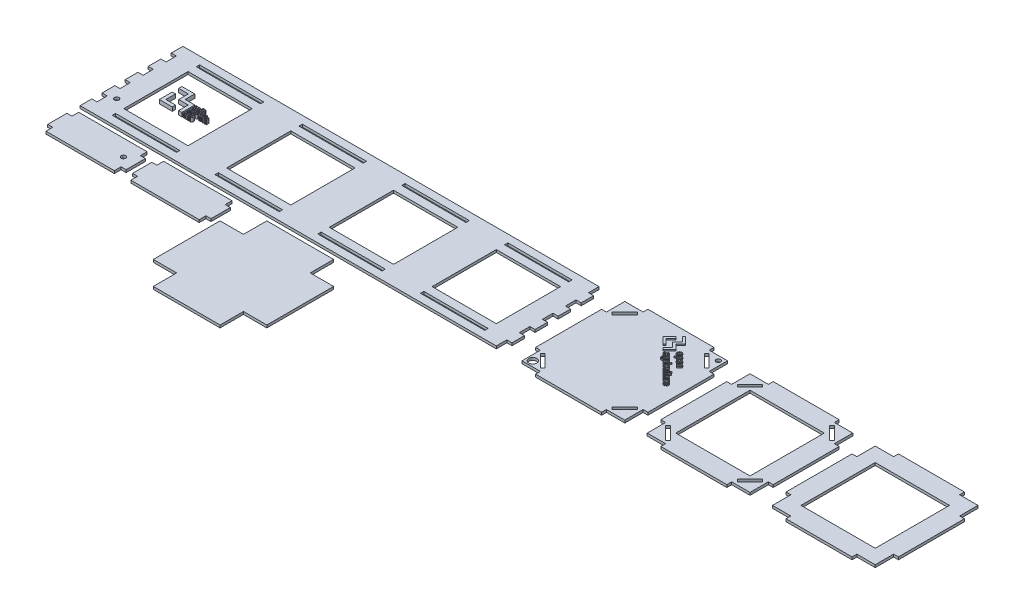
SolidWorks part; units mm, degrees
ref_plane "Front" through (0, 0, 0) normal (0, 0, 1) x (1, 0, 0)
ref_plane "Top" through (0, 0, 0) normal (0, 1, 0) x (1, 0, 0)
ref_plane "Right" through (0, 0, 0) normal (1, 0, 0) x (0, 0, -1)
sketch "Sketch1" plane through (0, 0, 0) normal (0, 1, 0) x (1, 0, 0)
  line L0 (0, 0) -> (152.4, 0) construction
  line L2 (-50.8, 50.8) -> (-50.8, -50.8) construction
  line L4 (50.8, 50.8) -> (50.8, -50.8) construction
  line L5 (-50.8, 50.8) -> (50.8, -50.8) construction
  line L6 (-50.8, -50.8) -> (50.8, 50.8) construction
  line L11 (50.8, 50.8) -> (152.4, 50.8)
  line L12 (50.8, 50.8) -> (50.8, -50.8) construction
  line L13 (50.8, -50.8) -> (152.4, -50.8)
  line L14 (152.4, 50.8) -> (152.4, -50.8) construction
  line L19 (-50.8, -50.8) -> (-152.4, -50.8)
  line L20 (-50.8, -50.8) -> (-50.8, 50.8) construction
  line L21 (-50.8, 50.8) -> (-152.4, 50.8)
  line L28 (50.8, -50.8) -> (-50.8, -50.8)
  line L34 (50.8, 50.8) -> (-50.8, 50.8)
  line L35 (-152.4, 50.8) -> (-152.4, -50.8) construction
  line L43 (-152.4, 50.8) -> (-254, 50.8)
  line L44 (-254, 50.8) -> (-254, -50.8) construction
  line L45 (-254, -50.8) -> (-152.4, -50.8)
  line L46 (152.4, 50.8) -> (152.4, 40.3352)
  line L47 (152.4, 40.3352) -> (157.48, 40.3352)
  line L48 (157.48, 40.3352) -> (157.48, 28.0162)
  line L49 (157.48, 28.0162) -> (152.4, 28.0162)
  line L50 (152.4, 28.0162) -> (152.4, 17.5514)
  line L51 (152.4, 17.5514) -> (157.48, 17.5514)
  line L63 (157.48, 17.5514) -> (157.48, 5.2324)
  line L64 (157.48, 5.2324) -> (152.4, 5.2324)
  line L65 (152.4, 5.2324) -> (152.4, -5.2324)
  line L66 (152.4, -5.2324) -> (157.48, -5.2324)
  line L67 (157.48, -5.2324) -> (157.48, -17.5514)
  line L68 (157.48, -17.5514) -> (152.4, -17.5514)
  line L69 (152.4, -17.5514) -> (152.4, -28.0162)
  line L70 (152.4, -28.0162) -> (157.48, -28.0162)
  line L71 (157.48, -28.0162) -> (157.48, -40.3352)
  line L72 (157.48, -40.3352) -> (152.4, -40.3352)
  line L73 (152.4, -40.3352) -> (152.4, -50.8)
  line L74 (-254, 50.8) -> (-259.08, 50.8)
  line L76 (-259.08, 39.2557) -> (-254, 39.2557)
  line L78 (-254, 29.0957) -> (-259.08, 29.0957)
  line L80 (-259.08, 16.4719) -> (-254, 16.4719)
  line L82 (-254, 6.3119) -> (-259.08, 6.3119)
  line L84 (-259.08, -6.3119) -> (-254, -6.3119)
  line L86 (-254, -16.4719) -> (-259.08, -16.4719)
  line L88 (-259.08, -29.0957) -> (-254, -29.0957)
  line L90 (-254, -39.2557) -> (-259.08, -39.2557)
  line L92 (-259.08, -50.8) -> (-254, -50.8)
  line L93 (157.48, 11.3919) -> (-254, 11.3919) construction
  line L94 (-254, 34.1757) -> (157.48, 34.1757) construction
  line L95 (-259.08, 50.8) -> (-259.08, 39.2557)
  line L96 (-259.08, 29.0957) -> (-259.08, 16.4719)
  line L97 (-254, 39.2557) -> (-254, 29.0957)
  line L98 (-254, 16.4719) -> (-254, 6.3119)
  line L99 (-254, -6.3119) -> (-254, -16.4719)
  line L100 (-254, -29.0957) -> (-254, -39.2557)
  line L101 (-254, -34.1757) -> (157.48, -34.1757) construction
  line L102 (-254, -11.3919) -> (157.48, -11.3919) construction
  line L103 (-259.08, 6.3119) -> (-259.08, -6.3119)
  line L104 (-259.08, -16.4719) -> (-259.08, -29.0957)
  line L105 (-259.08, -39.2557) -> (-259.08, -50.8)
  point P0 (0, 0)
  dimension "D1" = 101.6
  dimension "D2" = 101.6
  dimension "D3" = 5.08
  dimension "D4" = 12.319
  dimension "D5" = 10.16
extrude "Boss-Extrude1" add sketch "Sketch1" along normal blind 2.54
sketch "Sketch4" plane through (0, 2.54, 0) normal (0, 1, 0) x (1, 0, 0)
  line L0 (-152.4, 50.8) -> (-152.4, -50.8) construction
  line L1 (-152.4, 50.8) -> (-152.4, -50.8)
  line L2 (-50.8, 50.8) -> (-50.8, -50.8) construction
  line L3 (-50.8, 50.8) -> (-50.8, -50.8)
  line L4 (50.8, 50.8) -> (50.8, -50.8) construction
  line L5 (50.8, 50.8) -> (50.8, -50.8)
sketch "Sketch5" plane through (0, 2.54, 0) normal (0, 1, 0) x (1, 0, 0)
  line L0 (-254, -6.3119) -> (-254, 6.3119) construction
  line L1 (-152.4, 0) -> (-254, 0) construction
  line L2 (-152.4, 50.8) -> (-152.4, -50.8) construction
  line L3 (-152.4, 0) -> (-50.8, 0) construction
  line L4 (-50.8, 50.8) -> (-50.8, -50.8) construction
  line L5 (-50.8, 0) -> (50.8, 0) construction
  line L6 (50.8, 50.8) -> (50.8, -50.8) construction
  line L7 (50.8, 0) -> (152.4, 0) construction
  line L8 (152.4, -5.2324) -> (152.4, 5.2324) construction
  line L9 (-203.2, 0) -> (-203.2, -50.8) construction
  line L10 (-259.08, -50.8) -> (152.4, -50.8) construction
  line L11 (-101.6, 0) -> (-101.6, -50.8) construction
  line L12 (0, 0) -> (0, -50.8) construction
  line L13 (101.6, 0) -> (101.6, -50.8) construction
  line L14 (-171.45, -43.18) -> (-171.45, -50.8) construction
  line L15 (-234.95, -39.878) -> (-171.45, -39.878)
  line L16 (-234.95, -39.878) -> (-234.95, -43.18)
  line L17 (-234.95, -43.18) -> (-171.45, -43.18)
  line L18 (-171.45, -39.878) -> (-171.45, -43.18)
  line L19 (-234.95, -39.878) -> (-171.45, -43.18) construction
  line L20 (-234.95, -43.18) -> (-171.45, -39.878) construction
  line L21 (-133.35, -39.878) -> (-69.85, -39.878)
  line L22 (-133.35, -39.878) -> (-133.35, -43.18)
  line L23 (-133.35, -43.18) -> (-69.85, -43.18)
  line L24 (-69.85, -39.878) -> (-69.85, -43.18)
  line L25 (-133.35, -39.878) -> (-69.85, -43.18) construction
  line L26 (-133.35, -43.18) -> (-69.85, -39.878) construction
  line L27 (-31.75, -43.18) -> (31.75, -43.18)
  line L28 (-31.75, -43.18) -> (-31.75, -39.878)
  line L29 (-31.75, -39.878) -> (31.75, -39.878)
  line L30 (31.75, -43.18) -> (31.75, -39.878)
  line L31 (-31.75, -43.18) -> (31.75, -39.878) construction
  line L32 (-31.75, -39.878) -> (31.75, -43.18) construction
  line L33 (69.85, -43.18) -> (133.35, -43.18)
  line L34 (69.85, -43.18) -> (69.85, -39.878)
  line L35 (69.85, -39.878) -> (133.35, -39.878)
  line L36 (133.35, -43.18) -> (133.35, -39.878)
  line L37 (69.85, -43.18) -> (133.35, -39.878) construction
  line L38 (69.85, -39.878) -> (133.35, -43.18) construction
  line L39 (69.85, 39.878) -> (133.35, 43.18) construction
  line L40 (69.85, 43.18) -> (133.35, 39.878) construction
  line L41 (-31.75, 39.878) -> (31.75, 43.18) construction
  line L42 (-31.75, 43.18) -> (31.75, 39.878) construction
  line L43 (-133.35, 43.18) -> (-69.85, 39.878) construction
  line L44 (-133.35, 39.878) -> (-69.85, 43.18) construction
  line L45 (-234.95, 43.18) -> (-171.45, 39.878) construction
  line L46 (-234.95, 39.878) -> (-171.45, 43.18) construction
  line L47 (-171.45, 43.18) -> (-171.45, 50.8) construction
  line L48 (133.35, 43.18) -> (133.35, 39.878)
  line L49 (69.85, 39.878) -> (133.35, 39.878)
  line L50 (69.85, 43.18) -> (69.85, 39.878)
  line L51 (69.85, 43.18) -> (133.35, 43.18)
  line L52 (31.75, 43.18) -> (31.75, 39.878)
  line L53 (-31.75, 39.878) -> (31.75, 39.878)
  line L54 (-31.75, 43.18) -> (-31.75, 39.878)
  line L55 (-31.75, 43.18) -> (31.75, 43.18)
  line L56 (-69.85, 39.878) -> (-69.85, 43.18)
  line L57 (-133.35, 43.18) -> (-69.85, 43.18)
  line L58 (-133.35, 39.878) -> (-133.35, 43.18)
  line L59 (-133.35, 39.878) -> (-69.85, 39.878)
  line L60 (-171.45, 39.878) -> (-171.45, 43.18)
  line L61 (-234.95, 43.18) -> (-171.45, 43.18)
  line L62 (-234.95, 39.878) -> (-234.95, 43.18)
  line L63 (-234.95, 39.878) -> (-171.45, 39.878)
  line L65 (-234.95, 31.75) -> (-171.45, 31.75)
  line L66 (-234.95, 31.75) -> (-234.95, -31.75)
  line L67 (-234.95, -31.75) -> (-171.45, -31.75)
  line L68 (-171.45, 31.75) -> (-171.45, -31.75)
  line L69 (-234.95, 31.75) -> (-171.45, -31.75) construction
  line L70 (-234.95, -31.75) -> (-171.45, 31.75) construction
  line L71 (-133.35, 31.75) -> (-69.85, 31.75)
  line L72 (-133.35, 31.75) -> (-133.35, -31.75)
  line L73 (-133.35, -31.75) -> (-69.85, -31.75)
  line L74 (-69.85, 31.75) -> (-69.85, -31.75)
  line L75 (-133.35, 31.75) -> (-69.85, -31.75) construction
  line L76 (-133.35, -31.75) -> (-69.85, 31.75) construction
  line L77 (-31.75, 31.75) -> (31.75, 31.75)
  line L78 (-31.75, 31.75) -> (-31.75, -31.75)
  line L79 (-31.75, -31.75) -> (31.75, -31.75)
  line L80 (31.75, 31.75) -> (31.75, -31.75)
  line L81 (-31.75, 31.75) -> (31.75, -31.75) construction
  line L82 (-31.75, -31.75) -> (31.75, 31.75) construction
  line L83 (69.85, 31.75) -> (133.35, 31.75)
  line L84 (69.85, 31.75) -> (69.85, -31.75)
  line L85 (69.85, -31.75) -> (133.35, -31.75)
  line L86 (133.35, 31.75) -> (133.35, -31.75)
  line L87 (69.85, 31.75) -> (133.35, -31.75) construction
  line L88 (69.85, -31.75) -> (133.35, 31.75) construction
  circle A0 centre (-246.95, -26.75) radius 2.2225
  point P27 (-203.2, -41.529)
  point P32 (-101.6, -41.529)
  point P37 (0, -41.529)
  point P42 (101.6, -41.529)
  point P66 (101.6, 41.529)
  point P67 (0, 41.529)
  point P68 (-101.6, 41.529)
  point P69 (-203.2, 41.529)
  dimension "D5" = 4.445
  dimension "D7" = 5
  dimension "D1" = 7.62
  dimension "D2" = 3.302
  dimension "D3" = 63.5
  dimension "D4" = 63.5
  dimension "D6" = 12
extrude "Cut-Extrude2" cut sketch "Sketch5" against normal through all
sketch "Sketch6" plane through (0, 0, 0) normal (0, 1, 0) x (1, 0, 0)
  line L0 (0, 0) -> (228.6, 0) construction
  line L1 (228.6, 0) -> (228.6, 53.1812) construction
  line L2 (177.8, 50.8) -> (279.4, 50.8) construction
  line L3 (177.8, 50.8) -> (177.8, -50.8) construction
  line L4 (177.8, -50.8) -> (279.4, -50.8) construction
  line L5 (279.4, 50.8) -> (279.4, -50.8) construction
  line L6 (177.8, 50.8) -> (279.4, -50.8) construction
  line L7 (177.8, -50.8) -> (279.4, 50.8) construction
  line L8 (228.6, 0) -> (281.7812, 0) construction
  line L9 (228.6, 0) -> (228.6, -53.1812) construction
  line L10 (177.8, 32.639) -> (177.8, 50.8)
  line L11 (195.961, 55.5625) -> (261.239, 55.5625)
  line L12 (195.961, 55.5625) -> (195.961, 50.8)
  line L13 (195.961, 50.8) -> (261.239, 50.8) construction
  line L14 (261.239, 55.5625) -> (261.239, 50.8)
  line L15 (195.961, 55.5625) -> (261.239, 50.8) construction
  line L16 (195.961, 50.8) -> (261.239, 55.5625) construction
  line L17 (284.1625, -32.639) -> (279.4, -32.639)
  line L18 (284.1625, -32.639) -> (284.1625, 32.639)
  line L19 (284.1625, 32.639) -> (279.4, 32.639)
  line L20 (279.4, -32.639) -> (279.4, 32.639) construction
  line L21 (284.1625, -32.639) -> (279.4, 32.639) construction
  line L22 (284.1625, 32.639) -> (279.4, -32.639) construction
  line L23 (195.961, -55.5625) -> (261.239, -55.5625)
  line L24 (195.961, -55.5625) -> (195.961, -50.8)
  line L25 (195.961, -50.8) -> (261.239, -50.8) construction
  line L26 (261.239, -55.5625) -> (261.239, -50.8)
  line L27 (195.961, -55.5625) -> (261.239, -50.8) construction
  line L28 (195.961, -50.8) -> (261.239, -55.5625) construction
  line L29 (173.0375, 32.639) -> (177.8, 32.639)
  line L30 (173.0375, 32.639) -> (173.0375, -32.639)
  line L31 (173.0375, -32.639) -> (177.8, -32.639)
  line L32 (177.8, 32.639) -> (177.8, -32.639) construction
  line L33 (173.0375, 32.639) -> (177.8, -32.639) construction
  line L34 (173.0375, -32.639) -> (177.8, 32.639) construction
  line L35 (177.8, 50.8) -> (195.961, 50.8)
  line L36 (261.239, 50.8) -> (279.4, 50.8)
  line L37 (279.4, 50.8) -> (279.4, 32.639)
  line L38 (279.4, -32.639) -> (279.4, -50.8)
  line L39 (279.4, -50.8) -> (261.239, -50.8)
  line L40 (195.961, -50.8) -> (177.8, -50.8)
  line L41 (177.8, -50.8) -> (177.8, -32.639)
  line L42 (296.8625, 32.639) -> (296.8625, -32.639)
  line L43 (296.8625, 32.639) -> (301.625, 32.639)
  line L44 (301.625, 32.639) -> (301.625, 50.8)
  line L45 (301.625, 50.8) -> (319.786, 50.8)
  line L46 (319.786, 55.5625) -> (319.786, 50.8)
  line L47 (319.786, 55.5625) -> (385.064, 55.5625)
  line L48 (385.064, 55.5625) -> (385.064, 50.8)
  line L49 (385.064, 50.8) -> (403.225, 50.8)
  line L50 (403.225, 50.8) -> (403.225, 32.639)
  line L51 (407.9875, 32.639) -> (403.225, 32.639)
  line L52 (407.9875, -32.639) -> (407.9875, 32.639)
  line L53 (407.9875, -32.639) -> (403.225, -32.639)
  line L54 (403.225, -32.639) -> (403.225, -50.8)
  line L55 (403.225, -50.8) -> (385.064, -50.8)
  line L56 (385.064, -55.5625) -> (385.064, -50.8)
  line L57 (319.786, -55.5625) -> (385.064, -55.5625)
  line L58 (319.786, -55.5625) -> (319.786, -50.8)
  line L59 (319.786, -50.8) -> (301.625, -50.8)
  line L60 (301.625, -50.8) -> (301.625, -32.639)
  line L61 (296.8625, -32.639) -> (301.625, -32.639)
  line L62 (301.625, 50.8) -> (403.225, -50.8) construction
  line L63 (420.6875, 32.639) -> (420.6875, -32.639)
  line L64 (420.6875, 32.639) -> (425.45, 32.639)
  line L65 (425.45, 32.639) -> (425.45, 50.8)
  line L66 (425.45, 50.8) -> (443.611, 50.8)
  line L67 (443.611, 55.5625) -> (443.611, 50.8)
  line L68 (443.611, 55.5625) -> (508.889, 55.5625)
  line L69 (508.889, 55.5625) -> (508.889, 50.8)
  line L70 (508.889, 50.8) -> (527.05, 50.8)
  line L71 (527.05, 50.8) -> (527.05, 32.639)
  line L72 (531.8125, 32.639) -> (527.05, 32.639)
  line L73 (531.8125, -32.639) -> (531.8125, 32.639)
  line L74 (531.8125, -32.639) -> (527.05, -32.639)
  line L75 (527.05, -32.639) -> (527.05, -50.8)
  line L76 (527.05, -50.8) -> (508.889, -50.8)
  line L77 (508.889, -55.5625) -> (508.889, -50.8)
  line L78 (443.611, -55.5625) -> (508.889, -55.5625)
  line L79 (443.611, -55.5625) -> (443.611, -50.8)
  line L80 (443.611, -50.8) -> (425.45, -50.8)
  line L81 (425.45, -50.8) -> (425.45, -32.639)
  line L82 (420.6875, -32.639) -> (425.45, -32.639)
  line L83 (425.45, 50.8) -> (527.05, -50.8) construction
  line L84 (315.722, 36.703) -> (389.128, 36.703)
  line L85 (315.722, 36.703) -> (315.722, -36.703)
  line L86 (315.722, -36.703) -> (389.128, -36.703)
  line L87 (389.128, 36.703) -> (389.128, -36.703)
  line L88 (315.722, 36.703) -> (389.128, -36.703) construction
  line L89 (315.722, -36.703) -> (389.128, 36.703) construction
  line L91 (512.953, 36.703) -> (439.547, 36.703)
  line L92 (512.953, 36.703) -> (512.953, -36.703)
  line L93 (512.953, -36.703) -> (439.547, -36.703)
  line L94 (439.547, 36.703) -> (439.547, -36.703)
  line L95 (512.953, 36.703) -> (439.547, -36.703) construction
  line L96 (512.953, -36.703) -> (439.547, 36.703) construction
  point P22 (175.4187, 0)
  point P67 (352.425, 0)
  point P72 (476.25, 0)
  dimension "D1" = 101.6
  dimension "D2" = 101.6
  dimension "D3" = 4.7625
  dimension "D4" = 65.278
  dimension "D5" = 228.6
  dimension "D7" = 12.7
  dimension "D8" = 73.406
  dimension "D6" = 3
extrude "Boss-Extrude2" add sketch "Sketch6" along normal blind 2.54 separate body
sketch "Sketch7" plane through (0, 0, 0) normal (0, 1, 0) x (1, 0, 0)
  line L0 (-234.95, 39.878) -> (-234.95, -27.686) construction
  line L1 (-254.08, -57.15) -> (-186.516, -57.15)
  line L2 (-254.08, -57.15) -> (-254.08, -63.8175)
  line L3 (-254.08, -89.535) -> (-186.516, -89.535)
  line L4 (-186.516, -57.15) -> (-186.516, -63.8175)
  line L5 (-254.08, -57.15) -> (-186.516, -89.535) construction
  line L6 (-254.08, -89.535) -> (-186.516, -57.15) construction
  line L7 (-234.95, 31.75) -> (-234.95, -31.75) construction
  line L8 (-234.95, -27.686) -> (-234.95, -31.75) construction
  line L9 (177.8, -32.639) -> (177.8, -50.8) construction
  line L10 (177.8, -50.8) -> (195.961, -50.8) construction
  line L12 (-254.08, -63.8175) -> (-259.08, -63.8175)
  line L13 (182.9292, -33.0985) -> (195.5015, -45.6708) construction
  line L14 (182.9292, -33.0985) -> (180.5943, -35.4333) construction
  line L15 (180.5943, -35.4333) -> (193.1667, -48.0057) construction
  line L16 (195.5015, -45.6708) -> (193.1667, -48.0057) construction
  line L17 (182.9292, -33.0985) -> (193.1667, -48.0057) construction
  line L18 (180.5943, -35.4333) -> (195.5015, -45.6708) construction
  line L19 (-259.08, -63.8175) -> (-259.08, -82.8675)
  line L20 (-259.08, -82.8675) -> (-254.08, -82.8675)
  line L21 (177.8, -32.639) -> (195.961, -50.8) construction
  line L22 (188.0479, -40.5521) -> (186.8805, -41.7195) construction
  line L23 (-254.08, -82.8675) -> (-254.08, -89.535)
  line L24 (-186.516, -63.8175) -> (-181.516, -63.8175)
  line L25 (-181.516, -63.8175) -> (-181.516, -82.8675)
  line L26 (-181.516, -82.8675) -> (-186.516, -82.8675)
  line L27 (-186.516, -82.8675) -> (-186.516, -89.535)
  line L28 (-259.08, -50.8) -> (152.4, -50.8) construction
  line L29 (-259.08, -39.2557) -> (-259.08, -50.8) construction
  line L30 (-170.166, -57.15) -> (-102.602, -57.15)
  line L31 (-170.166, -57.15) -> (-170.166, -63.8175)
  line L32 (-170.166, -89.535) -> (-102.602, -89.535)
  line L33 (-102.602, -57.15) -> (-102.602, -63.8175)
  line L34 (-170.166, -63.8175) -> (-175.166, -63.8175)
  line L35 (-175.166, -63.8175) -> (-175.166, -82.8675)
  line L36 (-175.166, -82.8675) -> (-170.166, -82.8675)
  line L37 (-170.166, -82.8675) -> (-170.166, -89.535)
  line L38 (-102.602, -63.8175) -> (-97.602, -63.8175)
  line L39 (-97.602, -63.8175) -> (-97.602, -82.8675)
  line L40 (-97.602, -82.8675) -> (-102.602, -82.8675)
  line L41 (-102.602, -82.8675) -> (-102.602, -89.535)
  line L42 (-170.166, -57.15) -> (-102.602, -89.535) construction
  line L43 (-170.166, -89.535) -> (-102.602, -57.15) construction
  point P0 (-220.298, -73.3425)
  point P14 (188.0479, -40.5521)
  point P38 (-136.384, -73.3425)
  dimension "D1" = 32.385
  dimension "D2" = 4.064
  dimension "D3" = 3.302
  dimension "D4" = 19.05
  dimension "D5" = 17.78
  dimension "D6" = 5
  dimension "D7" = 6.35
  dimension "D9" = 6.35
  dimension "D8" = 2
extrude "Boss-Extrude3" add sketch "Sketch7" along normal blind 2.54 separate body
sketch "Sketch8" plane through (0, 2.54, 0) normal (0, 1, 0) x (1, 0, 0)
  line L0 (180.5943, -35.4333) -> (193.1667, -48.0057) construction
  line L1 (195.5015, -45.6708) -> (193.1667, -48.0057) construction
  line L2 (182.9292, -33.0985) -> (195.5015, -45.6708) construction
  line L3 (182.9292, -33.0985) -> (180.5943, -35.4333) construction
  line L4 (180.5943, -35.4333) -> (193.1667, -48.0057)
  line L5 (195.5015, -45.6708) -> (193.1667, -48.0057)
  line L6 (182.9292, -33.0985) -> (195.5015, -45.6708)
  line L7 (182.9292, -33.0985) -> (180.5943, -35.4333)
  line L8 (177.8, 50.8) -> (279.4, -50.8) construction
  line L9 (195.5015, 45.6708) -> (182.9292, 33.0985)
  line L10 (195.5015, 45.6708) -> (193.1667, 48.0057)
  line L11 (193.1667, 48.0057) -> (180.5943, 35.4333)
  line L12 (182.9292, 33.0985) -> (180.5943, 35.4333)
  line L13 (274.2708, 33.0985) -> (261.6985, 45.6708)
  line L14 (274.2708, 33.0985) -> (276.6057, 35.4333)
  line L15 (276.6057, 35.4333) -> (264.0333, 48.0057)
  line L16 (261.6985, 45.6708) -> (264.0333, 48.0057)
  line L17 (261.6985, -45.6708) -> (274.2708, -33.0985)
  line L18 (261.6985, -45.6708) -> (264.0333, -48.0057)
  line L19 (264.0333, -48.0057) -> (276.6057, -35.4333)
  line L20 (274.2708, -33.0985) -> (276.6057, -35.4333)
  line L21 (301.625, -32.639) -> (319.786, -50.8) construction
  line L22 (304.4193, -35.4333) -> (306.7542, -33.0985)
  line L23 (306.7542, -33.0985) -> (319.3265, -45.6708)
  line L24 (319.3265, -45.6708) -> (316.9917, -48.0057)
  line L25 (310.7055, -41.7195) -> (313.0404, -39.3846) construction
  line L26 (304.4193, -35.4333) -> (316.9917, -48.0057)
  line L27 (301.625, 50.8) -> (403.225, -50.8) construction
  line L28 (306.7542, 33.0985) -> (304.4193, 35.4333)
  line L29 (316.9917, 48.0057) -> (304.4193, 35.4333)
  line L30 (316.9917, 48.0057) -> (319.3265, 45.6708)
  line L31 (319.3265, 45.6708) -> (306.7542, 33.0985)
  line L32 (385.5235, 45.6708) -> (387.8583, 48.0057)
  line L33 (400.4307, 35.4333) -> (387.8583, 48.0057)
  line L34 (400.4307, 35.4333) -> (398.0958, 33.0985)
  line L35 (398.0958, 33.0985) -> (385.5235, 45.6708)
  line L36 (398.0958, -33.0985) -> (400.4307, -35.4333)
  line L37 (387.8583, -48.0057) -> (400.4307, -35.4333)
  line L38 (387.8583, -48.0057) -> (385.5235, -45.6708)
  line L39 (385.5235, -45.6708) -> (398.0958, -33.0985)
  circle A0 centre (228.6, 0) radius 20.7898 construction
  circle A1 centre (228.6, 0) radius 20.7898 construction
  circle A2 centre (228.6, 0) radius 20.7898 construction
  circle A3 centre (228.6, 0) radius 20.7898 construction
  circle A4 centre (352.425, 0) radius 51.9059 construction
  point P28 (228.6, 0)
  point P58 (352.425, 0)
  dimension "D1" = 4
  dimension "D2" = 4
extrude "Cut-Extrude3" cut sketch "Sketch8" against normal through all
sketch "Sketch10" plane through (0, 2.54, 0) normal (0, 1, 0) x (1, 0, 0)
  line L0 (-171.45, 31.75) -> (-234.95, 31.75) construction
  line L1 (-69.85, 31.75) -> (-133.35, 31.75) construction
  line L2 (31.75, 31.75) -> (-31.75, 31.75) construction
  line L3 (133.35, 31.75) -> (69.85, 31.75) construction
  line L4 (-196.85, 31.75) -> (-209.55, 31.75)
  line L5 (-95.25, 31.75) -> (-107.95, 31.75)
  line L6 (6.35, 31.75) -> (-6.35, 31.75)
  line L7 (107.95, 31.75) -> (95.25, 31.75)
  line L8 (-234.95, -27.686) -> (-171.45, -27.686)
  line L9 (-203.2, -27.686) -> (-203.2, -31.75) construction
  line L14 (-234.95, 31.75) -> (-234.95, -31.75) construction
  line L15 (-171.45, -31.75) -> (-171.45, 31.75) construction
  line L16 (-234.95, -31.75) -> (-171.45, -31.75) construction
  line L17 (-133.35, -27.686) -> (-69.85, -27.686)
  line L18 (-133.35, 31.75) -> (-133.35, -31.75) construction
  line L19 (-69.85, -31.75) -> (-69.85, 31.75) construction
  line L20 (-31.75, -27.686) -> (31.75, -27.686)
  line L21 (-31.75, 31.75) -> (-31.75, -31.75) construction
  line L22 (31.75, -31.75) -> (31.75, 31.75) construction
  line L23 (69.85, -27.686) -> (133.35, -27.686)
  line L24 (69.85, 31.75) -> (69.85, -31.75) construction
  line L25 (133.35, -31.75) -> (133.35, 31.75) construction
  line L27 (-234.95, 31.75) -> (-234.95, -27.686) construction
  arc A0 (-209.55, 31.75) -> (-196.85, 31.75) centre (-203.2, 31.75) ccw
  arc A1 (-107.95, 31.75) -> (-95.25, 31.75) centre (-101.6, 31.75) ccw
  arc A2 (-6.35, 31.75) -> (6.35, 31.75) centre (0, 31.75) ccw
  arc A3 (95.25, 31.75) -> (107.95, 31.75) centre (101.6, 31.75) ccw
  dimension "D1" = 12.7
  dimension "D2" = 4.064
sketch "Sketch11" plane through (0, 0, 0) normal (0, 1, 0) x (1, 0, 0)
  line L0 (-133.35, -31.75) -> (-133.35, -39.878) construction
  line L5 (-68.138, -80.264) -> (-2.098, -80.264) construction
  line L6 (-68.138, -80.264) -> (-68.138, -146.304) construction
  line L7 (-68.138, -146.304) -> (-2.098, -146.304) construction
  line L8 (-2.098, -80.264) -> (-2.098, -146.304) construction
  line L9 (-68.138, -80.264) -> (-2.098, -146.304) construction
  line L10 (-68.138, -146.304) -> (-2.098, -80.264) construction
  line L11 (-68.138, -80.264) -> (-91.252, -80.264)
  line L12 (-91.252, -80.264) -> (-91.252, -146.304)
  line L13 (-91.252, -146.304) -> (-68.138, -146.304)
  line L14 (-68.138, -80.264) -> (-68.138, -57.15)
  line L15 (-68.138, -57.15) -> (-2.098, -57.15)
  line L16 (-2.098, -57.15) -> (-2.098, -80.264)
  line L17 (-2.098, -80.264) -> (21.016, -80.264)
  line L18 (21.016, -80.264) -> (21.016, -146.304)
  line L19 (21.016, -146.304) -> (-2.098, -146.304)
  line L20 (-2.098, -146.304) -> (-2.098, -169.418)
  line L21 (-2.098, -169.418) -> (-68.138, -169.418)
  line L22 (-68.138, -169.418) -> (-68.138, -146.304)
  line L23 (-259.08, -50.8) -> (152.4, -50.8) construction
  line L24 (-97.602, -82.8675) -> (-97.602, -63.8175) construction
  line L27 (133.35, -27.686) -> (133.35, -50.8) construction
  point P0 (-35.118, -113.284)
  dimension "D1" = 66.04
  dimension "D4" = 6.35
  dimension "D5" = 6.35
extrude "Boss-Extrude5" add sketch "Sketch11" along normal blind 2.54 separate body
sketch "Sketch12" plane through (0, 2.54, 0) normal (0, 1, 0) x (1, 0, 0)
  line L0 (-68.138, -80.264) -> (-2.098, -80.264)
  line L1 (-2.098, -80.264) -> (-2.098, -146.304)
  line L2 (-2.098, -146.304) -> (-68.138, -146.304)
  line L3 (-68.138, -80.264) -> (-68.138, -146.304)
sketch "Sketch13" plane through (0, 0, 0) normal (0, 1, 0) x (1, 0, 0)
  line L16 (-223.9443, 14.6616) -> (-211.1797, 14.6616)
  line L17 (-211.1797, 14.6616) -> (-211.1797, 5.1786)
  line L18 (-211.1797, 5.1786) -> (-201.7193, 5.1786)
  line L19 (239.1402, 49.5353) -> (245.5874, 43.0882)
  line L20 (245.5874, 43.0882) -> (240.7977, 38.2986)
  line L21 (240.7977, 38.2986) -> (245.5759, 33.5204)
  line L22 (245.5759, 33.5204) -> (239.1174, 27.0618)
  line L24 (237.5056, 28.6736) -> (242.3295, 33.4975)
  line L25 (242.3295, 33.4975) -> (237.5627, 38.2643)
  line L26 (237.5627, 38.2643) -> (242.3752, 43.0768)
  line L27 (242.3752, 43.0768) -> (237.5284, 47.9235)
  line L28 (237.5284, 47.9235) -> (239.1402, 49.5353)
  line L29 (234.3506, 44.7457) -> (235.9738, 43.1225)
  line L30 (235.9738, 43.1225) -> (231.1385, 38.2871)
  line L31 (231.1385, 38.2871) -> (235.9624, 33.4632)
  line L32 (235.9624, 33.4632) -> (234.3392, 31.84)
  line L33 (234.3392, 31.84) -> (227.892, 38.2871)
  line L34 (227.892, 38.2871) -> (234.3506, 44.7457)
  line L36 (239.5771, 26.9975) -> (266.5291, 0.0455) construction
  line L37 (247.4273, 32.1428) -> (285.1667, -5.5965) construction
  line L38 (237.5056, 28.6736) -> (239.1174, 27.0618)
  line L41 (-201.7193, 5.1786) -> (-201.7193, -7.6086)
  line L43 (-204.9105, -7.6086) -> (-204.9105, 1.9422)
  line L44 (-204.9105, 1.9422) -> (-214.3482, 1.9422)
  line L45 (-214.3482, 1.9422) -> (-214.3482, 11.4705)
  line L46 (-214.3482, 11.4705) -> (-223.9443, 11.4705)
  line L47 (-223.9443, 11.4705) -> (-223.9443, 14.6616)
  line L48 (-223.9443, 5.1786) -> (-220.7305, 5.1786)
  line L49 (-220.7305, 5.1786) -> (-220.7305, -4.3949)
  line L50 (-220.7305, -4.3949) -> (-211.1797, -4.3949)
  line L51 (-211.1797, -4.3949) -> (-211.1797, -7.6086)
  line L52 (-211.1797, -7.6086) -> (-223.9443, -7.6086)
  line L53 (-223.9443, -7.6086) -> (-223.9443, 5.1786)
  line L54 (-200.854, -7.608) -> (-149.188, -7.608) construction
  line L55 (-234.95, 31.75) -> (-171.45, -27.686) construction
  line L56 (-204.9105, -7.6086) -> (-201.7193, -7.6086)
  line L57 (-200.854, -7.608) -> (-200.854, 5.1786) construction
  line L58 (-200.854, 5.1786) -> (-201.7193, 5.1786) construction
  line L59 (-200.854, 1.9422) -> (-182.9615, 1.9422) construction
  line L60 (-200.854, -2.3557) -> (-181.4784, -2.3557) construction
  line L61 (-234.95, 31.75) -> (-234.95, -31.75) construction
  line L62 (-196.85, 6.35) -> (-209.55, 6.35) construction
  line L63 (-196.85, 6.35) -> (-196.85, -2.286) construction
  line L64 (-196.85, -2.286) -> (-209.55, -2.286) construction
  line L65 (-209.55, 6.35) -> (-209.55, -2.286) construction
  line L66 (-196.85, 6.35) -> (-209.55, -2.286) construction
  line L67 (-196.85, -2.286) -> (-209.55, 6.35) construction
  line L68 (-171.45, 31.75) -> (-234.95, 31.75) construction
  line L69 (-234.95, -27.686) -> (-171.45, -27.686) construction
  line L70 (-171.45, -31.75) -> (-171.45, 31.75) construction
  text T0 "mit" font "Arial" height in points 18
  text T1 "media" font "Arial" height in points 18
  text T2 "lab" font "Arial" height in points 18
  text T3 "open" font "Arial" height in points 24
  text T4 " agriculture" font "Arial" height in points 24
  point P56 (-194.7375, 4.459)
  dimension "D1" = 25.4
  dimension "D4" = 25.4
  dimension "D5" = 25.4
  dimension "D6" = 25.4
sketch "Sketch14" plane through (0, 2.54, 0) normal (0, 1, 0) x (1, 0, 0)
  line L0 (-181.516, -73.3425) -> (-193.7385, -73.3425) construction
  line L1 (-181.516, -82.8675) -> (-181.516, -63.8175) construction
  circle A0 centre (-193.7385, -73.3425) radius 2.2225
  circle A1 centre (-246.95, -26.75) radius 2.2225 construction
  dimension "D1" = 10
extrude "Cut-Extrude4" cut sketch "Sketch14" against normal through all
extrude "Boss-Extrude7" add sketch "Sketch13" along normal blind 3.81 separate body
sketch "Sketch15" plane through (0, 2.54, 0) normal (0, 1, 0) x (1, 0, 0)
  line L0 (177.8, -50.8) -> (186.8805, -41.7195) construction
  line L1 (180.5943, -35.4333) -> (193.1667, -48.0057) construction
  line L2 (183.1192, -51.5768) -> (183.1192, -50.8) construction
  line L3 (177.8, -50.8) -> (195.961, -50.8) construction
  line L4 (186.8805, -41.7195) -> (187.4298, -41.1702) construction
  line L5 (177.8, 50.8) -> (279.4, -50.8) construction
  line L6 (279.4, 50.8) -> (270.3195, 41.7195) construction
  line L7 (276.6057, 35.4333) -> (264.0333, 48.0057) construction
  circle A0 centre (183.1192, -45.4808) radius 3.95
  circle A1 centre (183.1192, -45.4808) radius 6.096 construction
  circle A2 centre (274.8598, 46.2598) radius 2.2225
  circle A3 centre (-193.7385, -73.3425) radius 2.2225 construction
  dimension "D1" = 7.9
  dimension "D2" = 12.192
extrude "Cut-Extrude5" cut sketch "Sketch15" against normal through all
sketch "Sketch16" plane through (0, 2.54, 0) normal (0, 1, 0) x (1, 0, 0)
  line L0 (315.722, 36.703) -> (315.722, -36.703) construction
  line L1 (318.897, 4.953) -> (481.6251, 4.953) construction
  line L2 (318.897, 24.003) -> (356.997, 24.003)
  line L3 (318.897, 24.003) -> (318.897, -14.097)
  line L4 (318.897, -14.097) -> (356.997, -14.097)
  line L6 (318.897, 24.003) -> (356.997, -14.097) construction
  line L7 (318.897, -14.097) -> (356.997, 24.003) construction
  line L8 (481.6251, 4.953) -> (337.947, 4.953) construction
  line L9 (356.997, 24.003) -> (356.997, 7.3274)
  line L10 (361.4118, 10.5046) -> (361.3272, 10.6511)
  line L11 (337.947, 24.003) -> (337.947, -14.097) construction
  line L12 (350.647, 10.033) -> (341.249, 10.033)
  line L13 (350.647, -0.127) -> (341.249, -0.127)
  line L14 (337.947, 10.033) -> (337.947, -0.127) construction
  line L15 (361.061, 10.033) -> (337.947, 10.033) construction
  line L16 (361.061, -0.127) -> (337.947, -0.127) construction
  line L17 (353.8503, 9.1658) -> (358.5112, 6.4427)
  line L18 (361.061, 4.953) -> (360.3382, 4.953) construction
  line L19 (361.061, 4.953) -> (337.947, 4.953) construction
  line L20 (376.3171, 4.953) -> (360.3382, 4.953) construction
  line L21 (350.647, 10.033) -> (350.647, -0.127) construction
  line L22 (356.997, -9.6369) -> (356.997, -14.097)
  line L23 (389.128, 36.703) -> (315.722, 36.703) construction
  line L24 (337.947, 13.335) -> (337.947, 13.843) construction
  line L25 (337.947, -3.429) -> (337.947, -3.937) construction
  line L26 (337.947, 13.335) -> (337.947, -3.429)
  arc A1 (361.4512, 3.3336) -> (364.7388, 8.5069) centre (364.617, 4.953) ccw
  arc A3 (364.8818, 16.6501) -> (361.3272, 10.6511) centre (364.7913, 12.6511) ccw
  arc A4 (361.4118, 10.5046) -> (364.7388, 8.5069) centre (364.8759, 12.5046) ccw
  arc A5 (353.8503, 9.1658) -> (350.647, 10.033) centre (350.647, 3.683) ccw
  arc A6 (355.5616, -2.4559) -> (350.647, -0.127) centre (350.647, -6.477) ccw
  arc A7 (361.4512, 3.3336) -> (358.5112, 6.4427) centre (354.6672, -0.1367) ccw
  arc A8 (341.249, -0.127) -> (337.947, -3.429) centre (341.249, -3.429) ccw
  arc A9 (337.947, 13.335) -> (341.249, 10.033) centre (341.249, 13.335) ccw
  arc A10 (355.5616, -2.4559) -> (364.8818, 16.6501) centre (364.617, 4.953) ccw
  point P4 (337.947, 4.953)
  point P28 (371.8905, 14.7821)
  dimension "D7" = 4
  dimension "D8" = 6.35
  dimension "D9" = 6.35
  dimension "D10" = 7.62
  dimension "D12" = 7.112
  dimension "D17" = 3.302
  dimension "D1" = 38.1
  dimension "D2" = 38.1
  dimension "D3" = 12.7
  dimension "D4" = 5.08
  dimension "D6" = 30
  dimension "D11" = 26.67
  dimension "D13" = 3.175
  dimension "D14" = 12.7
  dimension "D15" = 3.81
  dimension "D16" = 3.81
  dimension "D5" = 5.08
sketch "Sketch17" plane through (0, 2.54, 0) normal (0, 1, 0) x (1, 0, 0)
  line L1 (228.6, 55.5625) -> (228.6, -55.5625) construction
  line L5 (318.897, 24.003) -> (356.997, 24.003) construction
  line L6 (318.897, 24.003) -> (356.997, 24.003)
  line L7 (356.997, 24.003) -> (356.997, 7.3274) construction
  line L8 (318.897, 24.003) -> (318.897, -14.097) construction
  line L9 (318.897, -14.097) -> (356.997, -14.097) construction
  line L12 (261.239, 55.5625) -> (195.961, 55.5625) construction
  line L13 (195.961, -55.5625) -> (261.239, -55.5625) construction
  line L14 (356.997, -9.6369) -> (356.997, -14.097) construction
  line L15 (356.997, 24.003) -> (356.997, 7.3274)
  line L16 (350.647, 10.033) -> (341.249, 10.033)
  line L17 (337.947, 13.335) -> (337.947, -3.429)
  line L18 (341.249, -0.127) -> (350.647, -0.127)
  line L19 (361.3272, 10.6511) -> (361.4118, 10.5046)
  line L20 (358.5112, 6.4427) -> (353.8503, 9.1658)
  line L21 (350.647, 10.033) -> (341.249, 10.033)
  line L23 (341.249, -0.127) -> (350.647, -0.127)
  line L24 (361.3272, 10.6511) -> (361.4118, 10.5046)
  line L25 (358.5112, 6.4427) -> (353.8503, 9.1658)
  line L26 (318.897, 24.003) -> (356.997, 24.003)
  line L27 (318.897, 24.003) -> (318.897, -14.097)
  line L28 (318.897, -14.097) -> (356.997, -14.097)
  line L29 (356.997, -3.9255) -> (356.997, -14.097)
  line L30 (228.6, 8.382) -> (228.6, -8.382) construction
  line L31 (201.93, 0) -> (255.27, 0) construction
  line L32 (208.0731, 1.5292) -> (212.7339, 4.2292)
  line L34 (225.298, -5.08) -> (215.9, -5.08)
  line L35 (215.9, 5.08) -> (225.298, 5.08)
  arc A9 (212.7339, 4.2292) -> (215.9, 5.08) centre (215.9, -1.2362) cw
  arc A10 (205.0999, -1.6114) -> (208.0731, 1.5292) centre (211.8927, -5.0644) cw
  arc A11 (205.0999, -1.6114) -> (202.1617, 3.5484) centre (201.93, 0) cw
  arc A14 (210.9854, -7.4089) -> (202.6925, 11.6752) centre (201.93, 0) cw
  arc A15 (210.9854, -7.4089) -> (215.9, -5.08) centre (215.9, -11.43) cw
  arc A16 (225.298, -5.08) -> (228.6, -8.382) centre (225.298, -8.382) cw
  arc A17 (228.6, 8.382) -> (225.298, 5.08) centre (225.298, 8.382) cw
  arc A18 (337.947, 13.335) -> (341.249, 10.033) centre (341.249, 13.335) ccw
  arc A19 (341.249, -0.127) -> (337.947, -3.429) centre (341.249, -3.429) ccw
  arc A20 (355.5616, -2.4559) -> (350.647, -0.127) centre (350.647, -6.477) ccw
  arc A21 (355.5616, -2.4559) -> (364.8818, 16.6501) centre (364.617, 4.953) ccw
  arc A22 (364.8818, 16.6501) -> (361.3272, 10.6511) centre (364.7913, 12.6511) ccw
  arc A23 (361.4118, 10.5046) -> (364.7388, 8.5069) centre (364.8759, 12.5046) ccw
  arc A24 (361.4512, 3.3336) -> (364.7388, 8.5069) centre (364.617, 4.953) ccw
  arc A25 (361.4512, 3.3336) -> (358.5112, 6.4427) centre (354.6672, -0.1367) ccw
  arc A26 (353.8503, 9.1658) -> (350.647, 10.033) centre (350.647, 3.683) ccw
  arc A27 (337.947, 13.335) -> (341.249, 10.033) centre (341.249, 13.335) ccw
  arc A28 (341.249, -0.127) -> (337.947, -3.429) centre (341.249, -3.429) ccw
  arc A29 (355.5616, -2.4559) -> (350.647, -0.127) centre (350.647, -6.477) ccw
  arc A30 (355.5616, -2.4559) -> (364.8818, 16.6501) centre (364.617, 4.953) ccw
  arc A31 (364.8818, 16.6501) -> (361.3272, 10.6511) centre (364.7913, 12.6511) ccw
  arc A32 (361.4118, 10.5046) -> (364.7388, 8.5069) centre (364.8759, 12.5046) ccw
  arc A33 (361.4512, 3.3336) -> (364.7388, 8.5069) centre (364.617, 4.953) ccw
  arc A34 (361.4512, 3.3336) -> (358.5112, 6.4427) centre (354.6672, -0.1367) ccw
  arc A35 (353.8503, 9.1658) -> (350.647, 10.033) centre (350.647, 3.683) ccw
  arc A36 (202.6925, 11.6752) -> (202.1617, 3.5484) centre (202.4271, 7.6118) cw
  point P43 (228.6, 0)
  point P64 (228.6, 0)
  dimension "D4" = 11.7001
  dimension "D5" = 10.16
  dimension "D6" = 3.302
  dimension "D2" = 26.67
  dimension "D3" = 3.556
  dimension "D8" = 0.4971
  dimension "D9" = 7.62
  dimension "D7" = 16.764
  dimension "D10" = 4.6609
  dimension "D11" = 12.7
  dimension "D12" = 30.084
  dimension "D1" = 0
